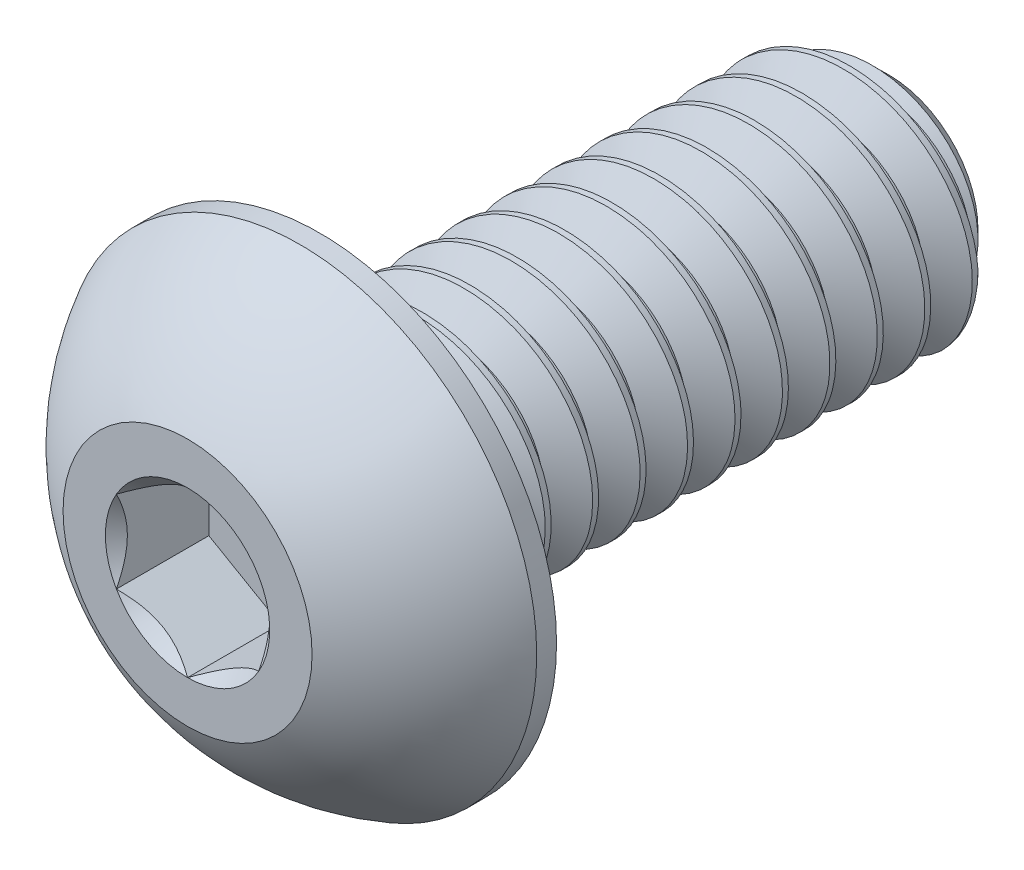
SolidWorks part; units mm, degrees
ref_plane "Front" through (0, 0, 0) normal (0, 0, 1) x (1, 0, 0)
ref_plane "Top" through (0, 0, 0) normal (0, 1, 0) x (1, 0, 0)
ref_plane "Right" through (0, 0, 0) normal (1, 0, 0) x (0, 0, -1)
sketch "Sketch1" plane through (0, 0, 0) normal (1, 0, 0) x (0, 0, -1)
  line L2 (2.2098, 2.0828) -> (11.7348, 2.0828)
  line L3 (11.7348, 2.0828) -> (11.7348, 0)
  line L4 (11.7348, 0) -> (2.2098, 0)
  line L6 (1.8783, 3.9624) -> (2.2098, 3.9624) construction
  line L7 (11.7348, 2.0828) -> (11.7348, -2.0828) construction
  line L8 (0, 0) -> (2.2098, 0) construction
  line L9 (2.2098, 3.9624) -> (2.2098, -3.9624) construction
  line L11 (2.2098, 2.0828) -> (2.2098, 0)
  line L13 (0, 1.1906) -> (0, -1.1906) construction
  line L14 (0, 1.1906) -> (0, 2.0828) construction
  arc A3 (0, 2.0828) -> (1.8783, 3.9624) centre (3.9638, 0) cw construction
  dimension "D1" = 0.3315
  dimension "Head Ht" = 2.2098
  dimension "Head Dia" = 7.9248
  dimension "Dia" = 4.1656
  dimension "Lg" = 9.525
  dimension "Hex" = 2.3813
revolve "Revolve1" add sketch "Sketch1" angle 360 mid plane about L4
sketch "Sketch3" plane through (0, 0, -11.7348) normal (0, 0, -1) x (-1, 0, 0)
  circle A0 centre (0, 0) radius 2.0828
curve "Helix/Spiral1" pitch 0.7937 height 10.3188 radius 2.0828 centre (0, 0, -11.7348) axis (0, 0, 1) start towards (0, 1, 0)
sketch "Sketch2" plane through (0, 0, 0) normal (1, 0, 0) x (0, 0, -1)
  line L0 (11.7348, 2.0828) -> (12.4293, 2.0828)
  line L1 (12.4293, 2.0828) -> (12.1317, 1.5672)
  line L2 (12.1317, 1.5672) -> (12.0325, 1.5672)
  line L3 (12.0325, 1.5672) -> (11.7348, 2.0828)
  line L4 (11.8836, 1.825) -> (12.2805, 1.825) construction
  dimension "D1" = 60
  dimension "D2" = 0.0992
  dimension "D3" = 0.3969
chamfer "Chamfer1" distance 0.5953 angle 45 1 edges at (0, 2.0828, -11.7348)
sweep "Cut-Sweep1" cut profiles "Sketch2" path "Helix/Spiral1"
sketch "Sketch7" plane through (0, 0, 0) normal (1, 0, 0) x (0, 0, -1)
  line L6 (1.8783, 3.9624) -> (2.2098, 3.9624) construction
  line L8 (0, 0) -> (2.2098, 0) construction
  line L11 (2.2098, 3.9624) -> (2.2098, -3.9624) construction
  line L12 (1.8783, 3.9624) -> (2.2098, 3.9624)
  line L13 (0, 0) -> (2.2098, 0)
  line L14 (0, 1.1906) -> (0, -1.1906) construction
  line L15 (2.2098, 3.9624) -> (2.2098, 0)
  line L16 (0, 2.0828) -> (0, 0)
  arc A2 (1.8783, 3.9624) -> (0, 2.0828) centre (3.9638, 0) ccw construction
  arc A3 (1.8783, 3.9624) -> (0, 2.0828) centre (3.9638, 0) ccw
revolve "Revolve2" add sketch "Sketch7" angle 360 mid plane about L13
sketch "Sketch5" plane through (0, 0, 0) normal (0, 0, 1) x (1, 0, 0)
  line L1 (1.1906, -0.6874) -> (1.1906, 0.6874)
  line L2 (1.1906, 0.6874) -> (0, 1.3748)
  line L3 (0, 1.3748) -> (-1.1906, 0.6874)
  line L4 (-1.1906, 0.6874) -> (-1.1906, -0.6874)
  line L5 (-1.1906, -0.6874) -> (0, -1.3748)
  line L6 (0, -1.3748) -> (1.1906, -0.6874)
  circle A0 centre (0, 0) radius 1.1906 construction
extrude "Cut-Extrude2" cut sketch "Sketch5" against normal blind 1.5469
sketch "Sketch6" plane through (0, 0, 0) normal (0, 0, 1) x (1, 0, 0)
  circle A0 centre (0, 0) radius 1.3748
extrude "Cut-Extrude3" cut sketch "Sketch6" against normal blind 1.5469 draft 45
sketch "Sketch9" [suppressed] plane through (0, 0, -1.4986) normal (0, 0, 1) x (1, 0, 0)
  circle A2 centre (0, 0) radius 1.4224
extrude "Boss-Extrude2" [suppressed] add sketch "Sketch9" against normal offset from surface (12.7 mm away) 31.75
sketch "Sketch10" plane through (0, 0, 0) normal (1, 0, 0) x (0, 0, -1)
  line L0 (11.7348, 2.0828) -> (11.7348, -2.0828) construction
  point P0 (10.5442, -2.0828)
  dimension "D1" = 1.1906
equation "\"D3@Helix/Spiral1\" = \"Lg@Sketch1\" + \"D4@Helix/Spiral1\""
equation "\"D2@Sketch2\" = \"D4@Helix/Spiral1\" * .125"
equation "\"D3@Sketch2\" = \"D4@Helix/Spiral1\" * .5"
equation "\"D1@Chamfer1\" = \"D4@Helix/Spiral1\" * .75"
equation "\"D1@Cut-Extrude2\" = \"Head Ht@Sketch1\" * .7"
equation "\"D1@Sketch1\" = \"Head Ht@Sketch1\" * .15"
equation "\"D1@Sketch10\" = \"D4@Helix/Spiral1\" * 1.5"
equation "\"D1@Cut-Extrude3\" = \"D1@Cut-Extrude2\""
